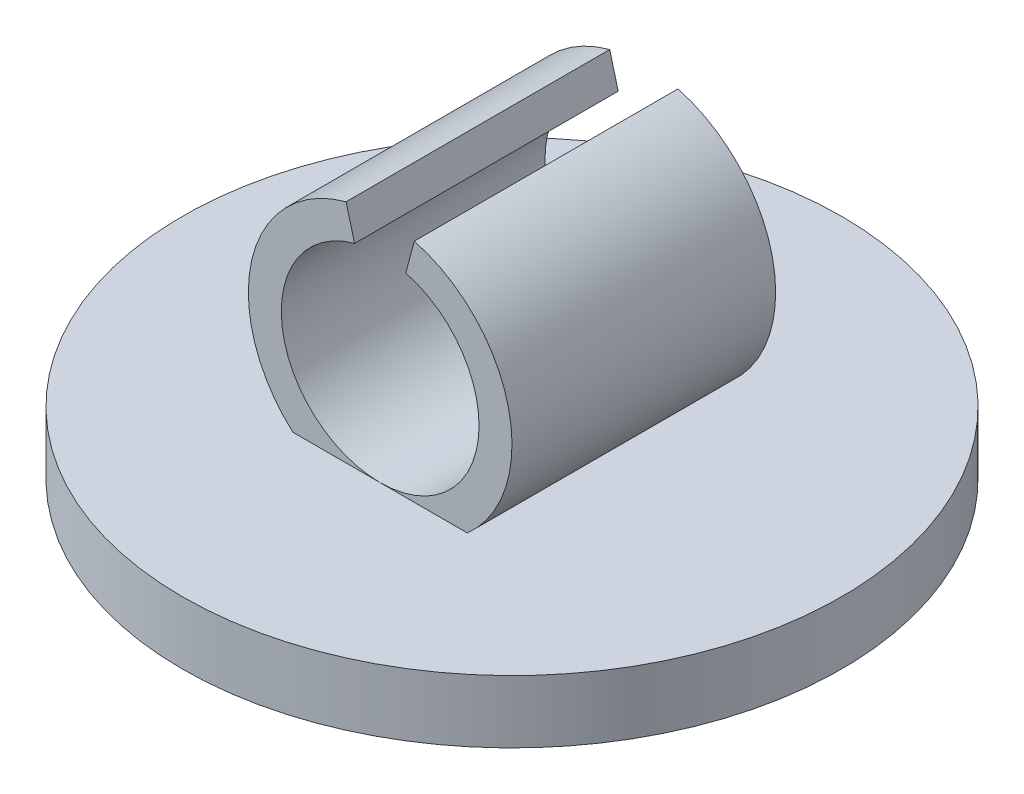
SolidWorks part; units mm, degrees
ref_plane "Alzado" through (0, 0, 0) normal (0, 0, 1) x (1, 0, 0)
ref_plane "Planta" through (0, 0, 0) normal (0, 1, 0) x (1, 0, 0)
ref_plane "Vista lateral" through (0, 0, 0) normal (1, 0, 0) x (0, 0, -1)
sketch "Croquis1" plane through (0, 0, 0) normal (0, 0, 1) x (1, 0, 0)
  line L0 (0, 0) -> (0, 24.5055) construction
  line L1 (0, 0) -> (3.75, 0)
  line L2 (3.75, 0) -> (3.75, 7.5)
  line L3 (3.75, 7.5) -> (25, 7.5)
  line L4 (25, 12.2528) -> (0, 12.2528)
  line L5 (25, 7.5) -> (25, 12.2528)
  line L6 (0, 0) -> (0, 12.2528)
  dimension "D1" = 7.5
  dimension "D2" = 25
  dimension "D3" = 3.75
  dimension "D4" = 4.7528
revolve "Revolución1" add sketch "Croquis1" angle 360 about L0
sketch "Croquis2" plane through (0, 0, 0) normal (0, 0, 1) x (1, 0, 0)
  line L0 (0, 12.2528) -> (0, 19.7528) construction
  line L3 (-1.9411, 26.9972) -> (-2.5882, 29.412)
  line L5 (1.9411, 26.9972) -> (2.5882, 29.412)
  arc A0 (-1.9411, 26.9972) -> (1.9411, 26.9972) centre (0, 19.7528) ccw
  arc A3 (-2.5882, 29.412) -> (2.5882, 29.412) centre (0, 19.7528) ccw
extrude "Saliente-Extruir1" add sketch "Croquis2" along normal blind 10 and the other way blind 10
